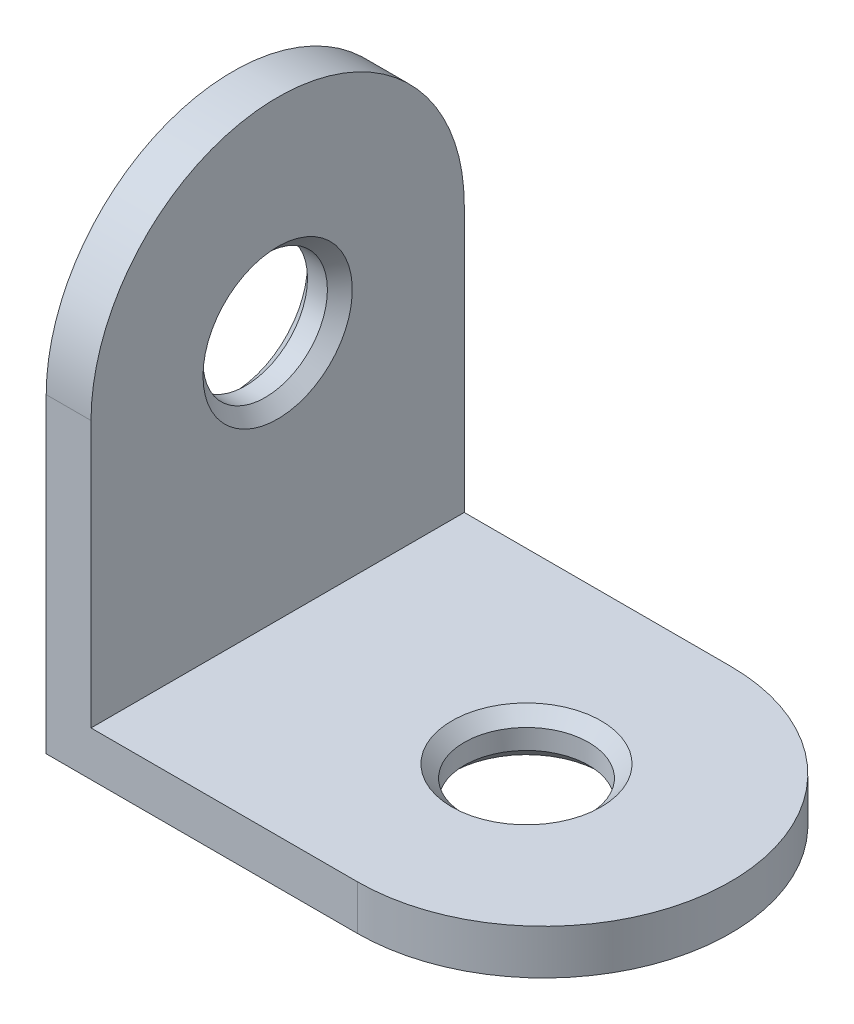
SolidWorks part; units mm, degrees
ref_plane "Front Plane" through (0, 0, 0) normal (0, 0, 1) x (1, 0, 0)
ref_plane "Top Plane" through (0, 0, 0) normal (0, 1, 0) x (1, 0, 0)
ref_plane "Right Plane" through (0, 0, 0) normal (1, 0, 0) x (0, 0, -1)
sketch "Sketch1" plane through (0, 0, 0) normal (0, 0, 1) x (1, 0, 0)
  line L0 (0, 0) -> (20, 0)
  line L1 (20, 0) -> (20, 1.8)
  line L2 (20, 1.8) -> (1.8, 1.8)
  line L3 (1.8, 1.8) -> (1.8, 20)
  line L4 (1.8, 20) -> (0, 20)
  line L5 (0, 20) -> (0, 0)
  dimension "D1" = 20
  dimension "D2" = 1.8
extrude "Boss-Extrude1" add sketch "Sketch1" along normal blind 15
fillet "Fillet1" 2 edges at (0.9, 20, 15) (0.9, 20, 0) type full round first side face at (7.2667, 7.2667, 15) second side face at (7.2667, 7.2667, 0) middle face at (0.9, 20, 7.5)
fillet "Fillet2" 2 edges at (20, 0.9, 15) (20, 0.9, 0) type full round first side face at (7.2667, 4.7667, 15) second side face at (7.2667, 4.7667, 0) middle face at (20, 0.9, 7.5)
sketch "Sketch2" plane through (1.8, 0, 0) normal (1, 0, 0) x (0, 0, -1)
  line L0 (-7.5, 1.8) -> (-7.5, 11.8) construction
  line L1 (-15, 1.8) -> (0, 1.8) construction
  circle A0 centre (-7.5, 11.8) radius 2.5
  dimension "D2" = 5
  dimension "D1" = 10
sketch "Sketch3" plane through (0, 1.8, 0) normal (0, 1, 0) x (1, 0, 0)
  line L0 (1.8, -7.5) -> (11.8, -7.5) construction
  line L1 (1.8, -15) -> (1.8, 0) construction
  circle A0 centre (11.8, -7.5) radius 2.5
  dimension "D2" = 5
  dimension "D1" = 10
extrude "Cut-Extrude1" cut sketch "Sketch3" against normal blind 10
extrude "Cut-Extrude2" cut sketch "Sketch2" against normal blind 10
chamfer "Chamfer1" distance 0.5 angle 45 4 edges at (11.8, 0, 10) (0, 11.8, 5) (9.3, 1.8, 7.5) (1.8, 11.8, 5)
